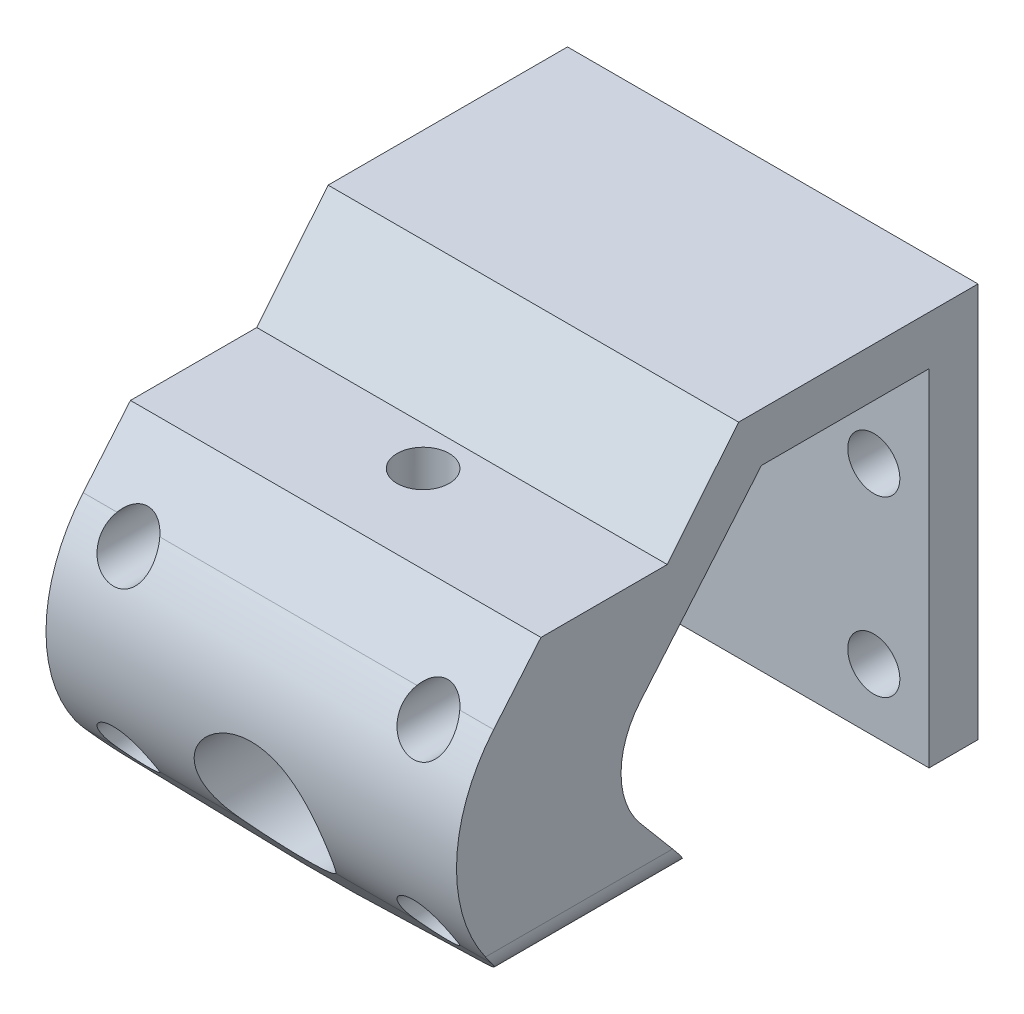
SolidWorks part; units mm, degrees
ref_plane "前视基准面" through (0, 0, 0) normal (0, 0, 1) x (1, 0, 0)
ref_plane "上视基准面" through (0, 0, 0) normal (0, 1, 0) x (1, 0, 0)
ref_plane "右视基准面" through (0, 0, 0) normal (1, 0, 0) x (0, 0, -1)
sketch "草图1" plane through (0, 0, 0) normal (1, 0, 0) x (0, 0, -1)
  line L0 (14.1075, 12.25) -> (3.7806, 12.25)
  line L1 (3.7806, 12.25) -> (-3.8242, 3.2211)
  line L2 (-3.8242, -3.2211) -> (3.7806, -12.25)
  line L3 (3.7806, -12.25) -> (14.1075, -12.25)
  line L4 (14.1075, -12.25) -> (14.1075, -9.25)
  line L5 (14.1075, -9.25) -> (9.3075, -9.25)
  line L6 (9.3075, -9.25) -> (9.3075, 9.25)
  line L7 (9.3075, 9.25) -> (14.1075, 9.25)
  line L8 (14.1075, 9.25) -> (14.1075, 12.25)
  line L9 (0, 0) -> (9.3075, 0) construction
  line L10 (14.3075, 12.45) -> (3.6876, 12.45)
  line L11 (3.6876, 12.45) -> (-3.9772, 3.3499)
  line L12 (-3.9772, -3.3499) -> (3.6876, -12.45)
  line L13 (3.6876, -12.45) -> (14.3075, -12.45)
  line L14 (14.3075, -12.45) -> (14.3075, -9.05)
  line L15 (14.3075, -9.05) -> (9.5075, -9.05)
  line L16 (9.5075, -9.05) -> (9.5075, 9.05)
  line L17 (9.5075, 9.05) -> (14.3075, 9.05)
  line L18 (14.3075, 9.05) -> (14.3075, 12.45)
  line L19 (0, -0.2) -> (9.3075, -0.2)
  line L20 (17.4075, 15.55) -> (2.2455, 15.55)
  line L21 (2.2455, 15.55) -> (-6.3482, 5.347)
  line L22 (-6.3482, -5.347) -> (2.2455, -15.55)
  line L23 (2.2455, -15.55) -> (17.4075, -15.55)
  line L24 (17.4075, -15.55) -> (17.4075, -5.95)
  line L28 (17.4075, 5.95) -> (17.4075, 15.55)
  line L29 (12.6075, 5.95) -> (17.4075, 5.95) construction
  line L30 (17.4075, -5.95) -> (12.6075, -5.95) construction
  line L31 (12.6075, -5.95) -> (12.6075, 5.95) construction
  line L32 (17.4075, 5.95) -> (17.4075, -5.95)
  line L33 (14.3075, 9.05) -> (14.3075, -9.05)
  line L34 (2.2455, 15.55) -> (-5.5992, 15.55)
  line L35 (-5.5992, 15.55) -> (-13.2705, 6.4421)
  line L36 (-13.2705, -6.4421) -> (-5.5992, -15.55)
  line L37 (-5.5992, -15.55) -> (2.2455, -15.55)
  line L38 (-10.2738, 10) -> (-2.2738, 10)
  line L39 (-2.2738, -10) -> (2.2455, -15.55)
  line L40 (-10.2738, -10) -> (-2.2738, -10)
  line L41 (-2.2738, 10) -> (2.2455, 15.55)
  arc A0 (-3.8242, 3.2211) -> (-3.8242, -3.2211) centre (0, 0) ccw
  arc A1 (-3.9772, 3.3499) -> (-3.9772, -3.3499) centre (0, 0) ccw
  arc A2 (-6.3482, 5.347) -> (-6.3482, -5.347) centre (0, 0) ccw
  arc A3 (-13.2705, 6.4421) -> (-13.2705, -6.4421) centre (-5.622, 0) ccw
  point P44 (-18.6966, 0)
  dimension "D5" = 5
  dimension "D10" = 10
  dimension "D1" = 3
  dimension "D2" = 10.3268
  dimension "D3" = 18.5
  dimension "D4" = 11.8049
  dimension "D6" = 4.8
  dimension "D9" = 6
  dimension "D11" = 8
  dimension "D12" = 20
  dimension "D7" = 0.2
  dimension "D8" = 3.3
extrude "凸台-拉伸1" add sketch "草图1" along normal blind 26 contours L21 A2 L22 L23 L24 L32 L28 L20 A1 L11 L10 L18 L33 L14 L13 L12 | A2 L21 L34 L35 L36 L37 L22 region at (0, 10.75, -17.004) region at (0, 0, 9.917)
sketch "草图2" plane through (0, 0, -17.4075) normal (0, 0, -1) x (-1, 0, 0)
  line L6 (-26, -9) -> (0, -9)
  line L7 (-26, -9) -> (-26, 9)
  line L8 (-26, 9) -> (0, 9)
  line L9 (0, -9) -> (0, 9)
  line L10 (-13, 9) -> (-13, -9) construction
  line L11 (-26, 0) -> (0, 0) construction
  line L12 (-26, 15.55) -> (0, 15.55) construction
  line L13 (-26, -15.55) -> (0, -15.55) construction
  line L14 (-26, -15.55) -> (-26, 15.55) construction
  line L15 (0, -15.55) -> (0, 15.55) construction
  circle A0 centre (-22.5, 5.5) radius 1.65
  circle A1 centre (-22.5, -5.5) radius 1.65
  circle A2 centre (-3.5, -5.5) radius 1.65
  circle A3 centre (-3.5, 5.5) radius 1.65
  point P12 (-3.5, -5.5)
  dimension "D3" = 3.3
  dimension "D1" = 18
  dimension "D2" = 26
  dimension "D4" = 11
  dimension "D5" = 19
extrude "切除-拉伸1" cut sketch "草图2" against normal through all contours A0 | A3 | A1 | A2
sketch "草图3" plane through (0, 0, 0) normal (-1, 0, 0) x (0, 0, 1)
  line L0 (-17.4075, -15.55) -> (-17.4075, 15.55) construction
  line L1 (-17.4075, -15.55) -> (10.737, -15.55)
  line L2 (-17.4075, -15.55) -> (-17.4075, -9.45)
  line L3 (-17.4075, -9.45) -> (10.737, -9.45)
  line L4 (10.737, -15.55) -> (10.737, -9.45)
  line L5 (-2.2455, -15.55) -> (-17.4075, -15.55) construction
  line L8 (-3.6876, -12.45) -> (-14.3075, -12.45) construction
  line L9 (13.2705, -6.4421) -> (10.2738, -10) construction
  dimension "D1" = 3.1
  dimension "D2" = 6.1
extrude "切除-拉伸2" cut sketch "草图3" against normal through all
ref_plane "基准面2" through (0, 0, 15.622) normal (0, 0, 1) x (1, 0, 0)
sketch "草图5" plane through (0, 0, 15.622) normal (0, 0, 1) x (1, 0, 0)
  line L0 (13, 6.4421) -> (13, -6.4421) construction
  line L1 (21.1454, 6.4421) -> (4.8546, 6.4421) construction
  line L2 (21.1454, -6.4421) -> (4.8546, -6.4421) construction
  line L3 (26, -9.45) -> (0, -9.45) construction
  circle A0 centre (13, -3.65) radius 4.1
  dimension "D1" = 5.8
  dimension "D2" = 8.2
extrude "切除-拉伸4" cut sketch "草图5" against normal up to next
sketch "草图6" plane through (0, -9.45, 0) normal (0, -1, 0) x (1, 0, 0)
  line L0 (13, 15.622) -> (13, 10.737) construction
  line L2 (26, 10.737) -> (0, 10.737) construction
  line L3 (12.045, 15.622) -> (-12.045, 15.622) construction
  circle A0 centre (13, 4.737) radius 1.65
  dimension "D1" = 3.3
  dimension "D2" = 6
extrude "切除-拉伸5" cut sketch "草图6" against normal through all
chamfer "倒角1" distance 2 angle 80 2 edges at (26, -9.45, 4.7881) (0, -9.45, 4.7881) first distance on face at (26, 2.7286, -0.655) first distance on face at (0, 2.7286, -0.655)
fillet "圆角1" radius 2 2 edges at (26, -7.45, 6.4727) (0, -7.45, 6.4727)
